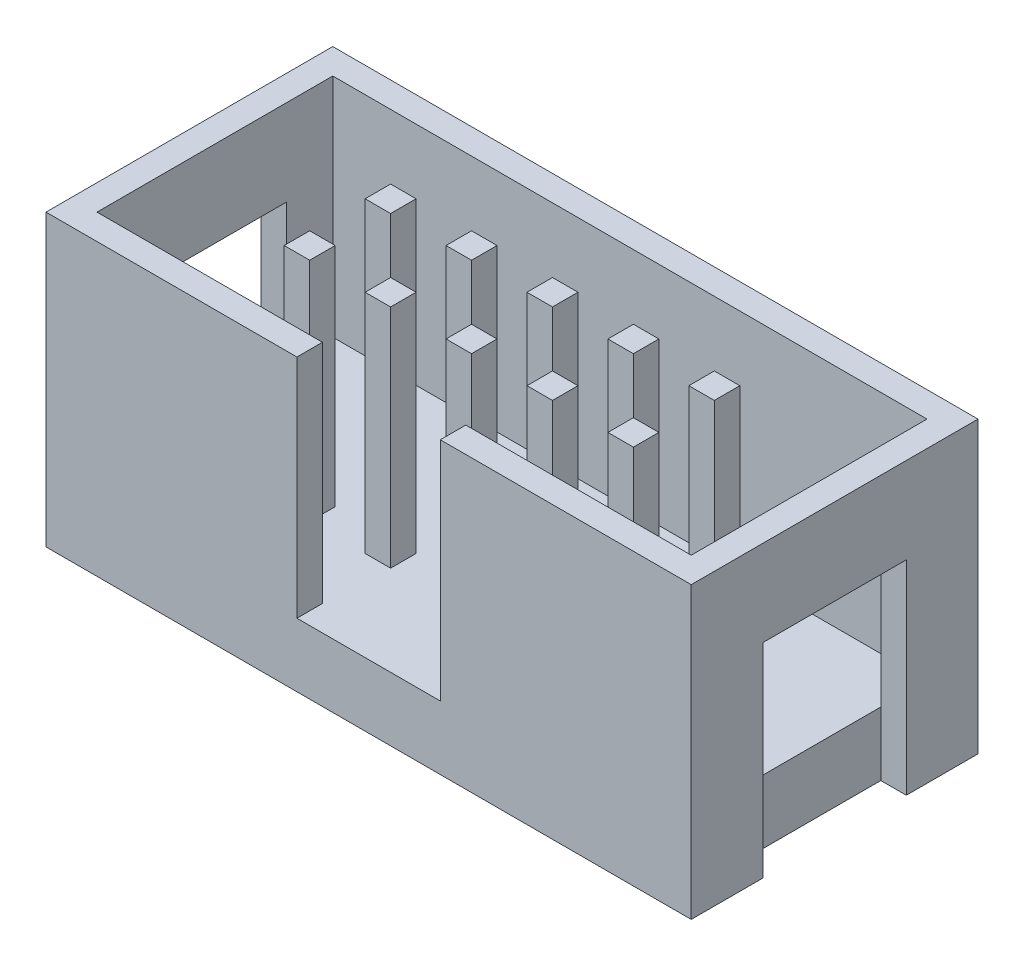
SolidWorks part; units mm, degrees
ref_plane "Front Plane" through (0, 0, 0) normal (0, 0, 1) x (1, 0, 0)
ref_plane "Top Plane" through (0, 0, 0) normal (0, 1, 0) x (1, 0, 0)
ref_plane "Right Plane" through (0, 0, 0) normal (1, 0, 0) x (0, 0, -1)
sketch "Sketch1" plane through (0, 0, 0) normal (0, 1, 0) x (1, 0, 0)
  line L1 (-39.7406, 29.0901) -> (-19.4906, 29.0901)
  line L2 (-39.7406, 29.0901) -> (-39.7406, 20.0901)
  line L3 (-39.7406, 20.0901) -> (-19.4906, 20.0901)
  line L4 (-19.4906, 29.0901) -> (-19.4906, 20.0901)
  dimension "D1" = 9
  dimension "D2" = 20.25
extrude "Boss-Extrude1" add sketch "Sketch1" along normal blind 9.1
sketch "Sketch2" plane through (0, 9.1, 0) normal (0, 1, 0) x (1, 0, 0)
  line L0 (-19.4906, 20.0901) -> (-19.4906, 29.0901) construction
  line L1 (-38.9406, 28.2901) -> (-20.2906, 28.2901)
  line L2 (-38.9406, 28.2901) -> (-38.9406, 20.8901)
  line L3 (-38.9406, 20.8901) -> (-20.2906, 20.8901)
  line L4 (-20.2906, 28.2901) -> (-20.2906, 20.8901)
  line L5 (-39.7406, 20.0901) -> (-19.4906, 20.0901) construction
  line L6 (-39.7406, 29.0901) -> (-39.7406, 20.0901) construction
  line L7 (-19.4906, 29.0901) -> (-39.7406, 29.0901) construction
  line L8 (-39.7406, 25.8601) -> (-19.4906, 25.8601) construction
  line L9 (-39.7406, 23.3201) -> (-19.4906, 23.3201) construction
  line L10 (-39.7406, 24.5901) -> (-19.4906, 24.5901) construction
  line L11 (-31.7556, 23.7201) -> (-31.7556, 22.9201)
  line L12 (-29.6156, 28.2901) -> (-29.6156, 20.8901) construction
  line L13 (-30.0156, 23.7201) -> (-30.0156, 22.9201)
  line L14 (-30.0156, 22.9201) -> (-29.2156, 22.9201)
  line L15 (-29.2156, 23.7201) -> (-29.2156, 22.9201)
  line L16 (-30.0156, 23.7201) -> (-29.2156, 23.7201)
  line L17 (-27.4756, 23.7201) -> (-27.4756, 22.9201)
  line L18 (-27.4756, 22.9201) -> (-26.6756, 22.9201)
  line L19 (-26.6756, 23.7201) -> (-26.6756, 22.9201)
  line L20 (-27.4756, 23.7201) -> (-26.6756, 23.7201)
  line L21 (-24.9356, 23.7201) -> (-24.1356, 23.7201)
  line L22 (-24.9356, 23.7201) -> (-24.9356, 22.9201)
  line L23 (-24.9356, 22.9201) -> (-24.1356, 22.9201)
  line L24 (-24.1356, 23.7201) -> (-24.1356, 22.9201)
  line L25 (-31.7556, 23.7201) -> (-32.5556, 23.7201)
  line L26 (-30.0156, 25.4601) -> (-29.2156, 25.4601)
  line L27 (-30.0156, 25.4601) -> (-30.0156, 26.2601)
  line L28 (-30.0156, 26.2601) -> (-29.2156, 26.2601)
  line L29 (-29.2156, 25.4601) -> (-29.2156, 26.2601)
  line L30 (-30.0156, 25.4601) -> (-29.2156, 26.2601) construction
  line L31 (-30.0156, 26.2601) -> (-29.2156, 25.4601) construction
  line L32 (-27.4756, 25.4601) -> (-26.6756, 25.4601)
  line L33 (-27.4756, 25.4601) -> (-27.4756, 26.2601)
  line L34 (-27.4756, 26.2601) -> (-26.6756, 26.2601)
  line L35 (-26.6756, 25.4601) -> (-26.6756, 26.2601)
  line L36 (-27.4756, 25.4601) -> (-26.6756, 26.2601) construction
  line L37 (-27.4756, 26.2601) -> (-26.6756, 25.4601) construction
  line L38 (-24.9356, 25.4601) -> (-24.1356, 25.4601)
  line L39 (-24.9356, 25.4601) -> (-24.9356, 26.2601)
  line L40 (-24.9356, 26.2601) -> (-24.1356, 26.2601)
  line L41 (-24.1356, 25.4601) -> (-24.1356, 26.2601)
  line L42 (-24.9356, 25.4601) -> (-24.1356, 26.2601) construction
  line L43 (-24.9356, 26.2601) -> (-24.1356, 25.4601) construction
  line L44 (-32.5556, 23.7201) -> (-32.5556, 22.9201)
  line L45 (-31.7556, 22.9201) -> (-32.5556, 22.9201)
  line L46 (-31.7556, 25.4601) -> (-31.7556, 26.2601)
  line L47 (-31.7556, 26.2601) -> (-32.5556, 26.2601)
  line L48 (-32.5556, 25.4601) -> (-32.5556, 26.2601)
  line L49 (-31.7556, 25.4601) -> (-32.5556, 25.4601)
  line L50 (-34.2956, 23.7201) -> (-34.2956, 22.9201)
  line L51 (-34.2956, 23.7201) -> (-35.0956, 23.7201)
  line L52 (-35.0956, 23.7201) -> (-35.0956, 22.9201)
  line L53 (-34.2956, 22.9201) -> (-35.0956, 22.9201)
  line L54 (-34.2956, 25.4601) -> (-34.2956, 26.2601)
  line L55 (-34.2956, 26.2601) -> (-35.0956, 26.2601)
  line L56 (-35.0956, 25.4601) -> (-35.0956, 26.2601)
  line L57 (-34.2956, 25.4601) -> (-35.0956, 25.4601)
  point P18 (-24.5356, 25.8601)
  point P19 (-29.6156, 25.8601)
  point P22 (-27.0756, 25.8601)
  dimension "D7" = 0.8
  dimension "D1" = 0.8
  dimension "D2" = 0.8
  dimension "D3" = 0.8
  dimension "D4" = 0.8
  dimension "D5" = 2.54
  dimension "D6" = 1.27
  dimension "D9" = 2.54
  dimension "D8" = 2.54
extrude "Cut-Extrude1" cut sketch "Sketch2" against normal blind 7.1 contours L3 L4 L1 L2
extrude "Boss-Extrude2" add sketch "Sketch2<3>" against normal blind 12.5 contours L38 L41 L40 L39 | L24 L21 L22 L23 | L20 L17 L18 L19 | L32 L35 L34 L33 | L26 L29 L28 L27 | L16 L13 L14 L15 | L45 L11 L25 L44 | L49 L46 L47 L48 | L57 L54 L55 L56 | L53 L50 L51 L52
sketch "Sketch2<3>" plane through (0, 9.1, 0) normal (0, 1, 0) x (1, 0, 0) same geometry as "Sketch2"
sketch "Sketch3" plane through (0, 0, -20.0901) normal (0, 0, 1) x (1, 0, 0)
  line L0 (-39.7406, 9.1) -> (-19.4906, 9.1) construction
  line L1 (-31.8656, 9.1) -> (-27.3656, 9.1)
  line L2 (-31.8656, 9.1) -> (-31.8656, 2)
  line L3 (-31.8656, 2) -> (-27.3656, 2)
  line L4 (-27.3656, 9.1) -> (-27.3656, 2)
  line L5 (-29.6156, 0) -> (-29.6156, 9.1) construction
  line L6 (-39.7406, 0) -> (-19.4906, 0) construction
  point P10 (-29.6156, 2)
  dimension "D1" = 7.1
  dimension "D2" = 4.5
extrude "Cut-Extrude2" cut sketch "Sketch3" against normal blind 2.1
sketch "Sketch5" plane through (-39.7406, 0, 0) normal (-1, 0, 0) x (0, 0, 1)
  line L0 (-24.5901, 0) -> (-24.5901, 9.1) construction
  line L1 (-26.8401, 0) -> (-22.3401, 0)
  line L2 (-26.8401, 0) -> (-26.8401, 6.4)
  line L3 (-26.8401, 6.4) -> (-22.3401, 6.4)
  line L4 (-22.3401, 0) -> (-22.3401, 6.4)
  line L7 (-29.0901, 0) -> (-20.0901, 0) construction
  line L8 (-29.0901, 9.1) -> (-20.0901, 9.1) construction
  point P7 (-24.5901, 6.4)
  dimension "D1" = 6.4
  dimension "D2" = 4.5
extrude "Cut-Extrude3" cut sketch "Sketch5" against normal up to surface (0.8 mm away) up to face at (-38.9406, 5.55, -24.5901)
sketch "Sketch6" plane through (-19.4906, 0, 0) normal (1, 0, 0) x (0, 0, -1)
  line L0 (24.5901, 0) -> (24.5901, 9.1) construction
  line L1 (22.3401, 0) -> (26.8401, 0)
  line L2 (22.3401, 0) -> (22.3401, 6.4)
  line L3 (22.3401, 6.4) -> (26.8401, 6.4)
  line L4 (26.8401, 0) -> (26.8401, 6.4)
  line L5 (20.0901, 0) -> (29.0901, 0) construction
  line L6 (20.0901, 9.1) -> (29.0901, 9.1) construction
  point P14 (24.5901, 6.4)
  dimension "D1" = 4.5
  dimension "D2" = 6.4
extrude "Cut-Extrude4" cut sketch "Sketch6" against normal up to surface (0.8 mm away) up to face at (-20.2906, 5.55, -24.5901)
sketch "Sketch8" plane through (-35.0956, 0, 0) normal (-1, 0, 0) x (0, 0, 1)
  line L1 (-26.2601, -1.4) -> (-22.9201, -1.4)
  line L2 (-26.2601, -1.4) -> (-26.2601, -3.4)
  line L3 (-26.2601, -3.4) -> (-22.9201, -3.4)
  line L4 (-22.9201, -1.4) -> (-22.9201, -3.4)
  line L5 (-23.7201, -3.4) -> (-22.9201, -3.4) construction
  line L6 (-26.2601, -3.4) -> (-26.2601, 0) construction
  line L7 (-22.9201, -3.4) -> (-22.9201, 0) construction
  dimension "D1" = 2
extrude "Cut-Extrude5" cut sketch "Sketch8" against normal through all
